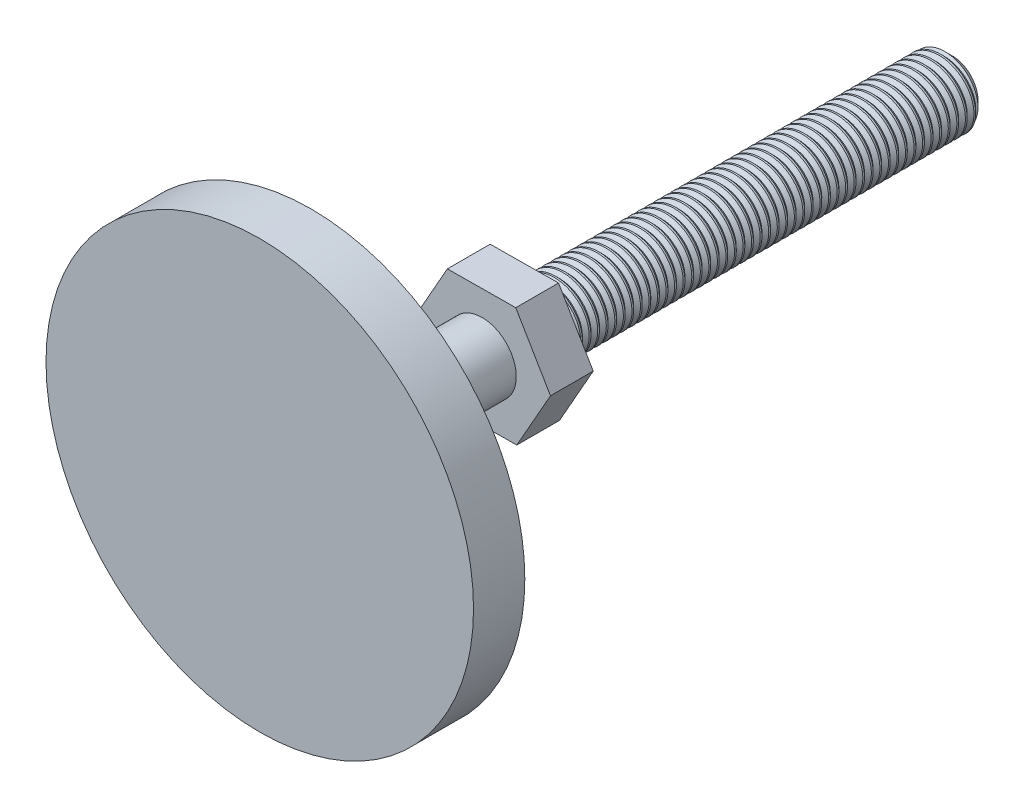
SolidWorks part; units mm, degrees
ref_plane "前视基准面" through (0, 0, 0) normal (0, 0, 1) x (1, 0, 0)
ref_plane "上视基准面" through (0, 0, 0) normal (0, 1, 0) x (1, 0, 0)
ref_plane "右视基准面" through (0, 0, 0) normal (1, 0, 0) x (0, 0, -1)
sketch "草图1" plane through (0, 0, 0) normal (0, 0, 1) x (1, 0, 0)
  circle A0 centre (0, 0) radius 25
  dimension "D1" = 50
extrude "凸台-拉伸1" add sketch "草图1" along normal blind 6
sketch "草图2" plane through (0, 0, 0) normal (1, 0, 0) x (0, 0, -1)
  line L0 (0, 0) -> (10, 0)
  line L1 (10, 0) -> (10, 9.654)
  line L2 (0, 25) -> (0, 0)
  line L3 (10, 9.654) -> (0, 25)
  dimension "D1" = 10
revolve "旋转1" add sketch "草图2" angle 360 about L0
sketch "草图3" plane through (0, 0, -10) normal (0, 0, -1) x (-1, 0, 0)
  circle A0 centre (0, 0) radius 5
  dimension "D1" = 10
extrude "凸台-拉伸2" add sketch "草图3" along normal blind 3
chamfer "倒角1" distance 1 angle 45 1 edges at (-5, 0, -13)
sketch "草图4" plane through (0, 0, -13) normal (0, 0, -1) x (-1, 0, 0)
  circle A0 centre (0, 0) radius 4
extrude "凸台-拉伸3" add sketch "草图4" along normal blind 7
sketch "草图5" plane through (0, 0, -20) normal (0, 0, -1) x (-1, 0, 0)
  line L1 (4.0591, 6.8938) -> (-3.9406, 6.9621)
  line L2 (-3.9406, 6.9621) -> (-7.9997, 0.0684)
  line L3 (-7.9997, 0.0684) -> (-4.0591, -6.8938)
  line L4 (-4.0591, -6.8938) -> (3.9406, -6.9621)
  line L5 (3.9406, -6.9621) -> (7.9997, -0.0684)
  line L6 (7.9997, -0.0684) -> (4.0591, 6.8938)
  circle A0 centre (0, 0) radius 8 construction
  dimension "D1" = 16
extrude "凸台-拉伸5" add sketch "草图5" along normal blind 5
sketch "草图6" plane through (0, 0, -25) normal (0, 0, -1) x (-1, 0, 0)
  circle A0 centre (0, 0) radius 4
  dimension "D1" = 8
extrude "凸台-拉伸6" add sketch "草图6" along normal blind 50
chamfer "倒角2" distance 1 angle 45 1 edges at (-4, 0, -75)
sketch "草图8" plane through (0, 0, -75) normal (0, 0, -1) x (-1, 0, 0)
  circle A0 centre (0, 0) radius 4
curve "螺旋线/涡状线1" pitch 1 height 50 turns 50
sketch "草图10" plane through (0, 0, 0) normal (1, 0, 0) x (0, 0, -1)
  line L0 (74.475, 4) -> (75.275, 4)
  line L1 (74.875, 4) -> (74.875, 3.6) construction
  line L2 (74.475, 4) -> (74.875, 3.6)
  line L3 (74.875, 3.6) -> (75.275, 4)
  dimension "D1" = 0.8
  dimension "D2" = 0.4
sweep "切除-扫描2" cut profiles "草图10" path "螺旋线/涡状线1"
